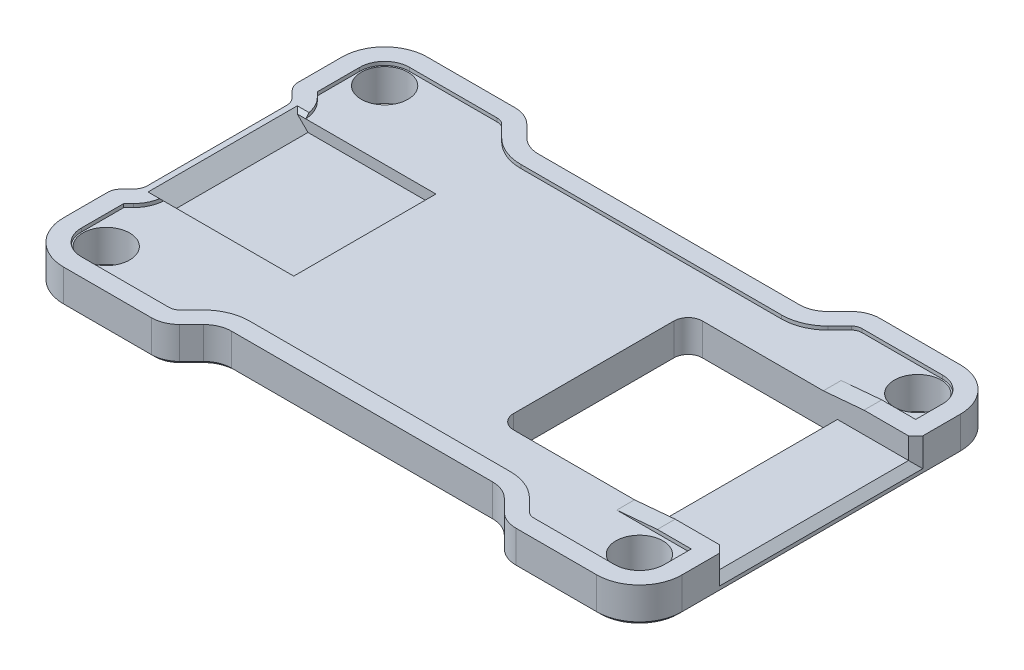
SolidWorks part; units mm, degrees
ref_plane "Front Plane" through (0, 0, 0) normal (0, 0, 1) x (1, 0, 0)
ref_plane "Top Plane" through (0, 0, 0) normal (0, 1, 0) x (1, 0, 0)
ref_plane "Right Plane" through (0, 0, 0) normal (1, 0, 0) x (0, 0, -1)
sketch "Sketch1" plane through (0, 0, 0) normal (0, 1, 0) x (1, 0, 0)
  line L0 (0, -5.29) -> (0, 5.29)
  line L1 (0, 5.29) -> (-1, 6.29)
  line L2 (-1, 6.29) -> (-1, 12.79)
  line L3 (-1, 12.79) -> (9, 12.79)
  line L4 (9, 12.79) -> (11, 10.79)
  line L5 (11, 10.79) -> (31, 10.79)
  line L6 (31, 10.79) -> (33, 12.79)
  line L7 (33, 12.79) -> (42.5, 12.79)
  line L8 (42.5, 12.79) -> (42.5, 6.64)
  line L9 (42.5, 6.64) -> (26.5, 6.64)
  line L10 (26.5, 6.64) -> (26.5, -6.64)
  line L11 (0, 0) -> (36.6809, 0) construction
  line L12 (42.5, -6.64) -> (26.5, -6.64)
  line L13 (42.5, -12.79) -> (42.5, -6.64)
  line L14 (33, -12.79) -> (42.5, -12.79)
  line L15 (31, -10.79) -> (33, -12.79)
  line L16 (11, -10.79) -> (31, -10.79)
  line L17 (9, -12.79) -> (11, -10.79)
  line L18 (-1, -12.79) -> (9, -12.79)
  line L19 (-1, -6.29) -> (-1, -12.79)
  line L20 (0, -5.29) -> (-1, -6.29)
  point P15 (26.5, 0)
  dimension "D1" = 5.29
  dimension "D2" = 1
  dimension "D3" = 1
  dimension "D4" = 6.5
  dimension "D5" = 10
  dimension "D6" = 2
  dimension "D7" = 20
  dimension "D8" = 2
  dimension "D9" = 2
  dimension "D10" = 9.5
  dimension "D11" = 6.15
  dimension "D12" = 16
extrude "Boss-Extrude1" add sketch "Sketch1" along normal blind 2.5
fillet "Fillet1" radius 3 4 edges at (-1, 1.25, -12.79) (42.5, 1.25, -12.79) (42.5, 1.25, 12.79) (-1, 1.25, 12.79)
fillet "Fillet2" radius 1 6 edges at (26.5, 1.25, 6.64) (26.5, 1.25, -6.64) (-1, 1.25, 6.29) (0, 1.25, 5.29) (0, 1.25, -5.29) (-1, 1.25, -6.29)
fillet "Fillet3" radius 2 8 edges at (33, 1.25, 12.79) (31, 1.25, 10.79) (9, 1.25, 12.79) (11, 1.25, 10.79) (33, 1.25, -12.79) (31, 1.25, -10.79) (11, 1.25, -10.79) (9, 1.25, -12.79)
sketch "Sketch3" plane through (0, 0, 0) normal (0, -1, 0) x (1, 0, 0)
  line L0 (42.5, 9.79) -> (42.5, 6.64) construction
  line L1 (42.5, 7.9165) -> (25.7261, 7.9165)
  line L2 (42.5, 7.9165) -> (42.5, -7.5646)
  line L3 (42.5, -7.5646) -> (25.7261, -7.5646)
  line L4 (25.7261, 7.9165) -> (25.7261, -7.5646)
extrude "Boss-Extrude2" add sketch "Sketch3" against normal offset from surface (1 mm away) 1.5 up to face at (18.1733, 2.5, 0)
chamfer "Chamfer1" distance 0.5 angle 45 3 edges at (42.5, 1.75, 6.64) (42.5, 1.75, -6.64) (42.5, 1, 0)
sketch "Sketch5" plane through (0, 2.5, 0) normal (0, 1, 0) x (1, 0, 0)
  line L0 (8.1716, 12.79) -> (2, 12.79) construction
  line L1 (-1, 9.79) -> (-1, 6.7042) construction
  line L2 (2, -12.79) -> (8.1716, -12.79) construction
  line L3 (-1, -6.7042) -> (-1, -9.79) construction
  line L4 (42.5, 7.14) -> (42.5, 9.79) construction
  line L5 (39.5, 12.79) -> (33.8284, 12.79) construction
  line L6 (42.5, -9.79) -> (42.5, -7.14) construction
  line L7 (33.8284, -12.79) -> (39.5, -12.79) construction
  circle A0 centre (2, 9.79) radius 1.65
  circle A1 centre (2, -9.79) radius 1.65
  circle A2 centre (39.5, 9.79) radius 1.65
  circle A3 centre (39.5, -9.79) radius 1.65
  dimension "D1" = 3.3
  dimension "D2" = 3
  dimension "D3" = 3
  dimension "D4" = 3
  dimension "D5" = 3
  dimension "D6" = 3.3
  dimension "D7" = 3
  dimension "D8" = 3
  dimension "D9" = 3.3
  dimension "D10" = 3
  dimension "D11" = 3
  dimension "D12" = 3.3
extrude "Cut-Extrude3" cut sketch "Sketch5" against normal through all
sketch "Sketch6" plane through (0, 2.5, 0) normal (0, 1, 0) x (1, 0, 0)
  line L0 (0, 4.8758) -> (0, -4.8758) construction
  line L1 (0.4, -5) -> (10.4, -5)
  line L2 (0.4, -5) -> (0.4, 5)
  line L3 (0.4, 5) -> (10.4, 5)
  line L4 (10.4, -5) -> (10.4, 5)
  line L5 (0.4, -5) -> (10.4, 5) construction
  line L6 (0.4, 5) -> (10.4, -5) construction
  point P0 (5.4, 0)
  dimension "D1" = 10
  dimension "D2" = 0.4
  dimension "D3" = 10
extrude "Cut-Extrude4" cut sketch "Sketch6" against normal blind 1
chamfer "Chamfer2" distance 0.25 angle 45 3 edges at (5.4, 2.5, 5) (10.4, 2.5, 0) (5.4, 2.5, -5)
chamfer "Chamfer3" distance 0.25 angle 45 32 edges at (41.6213, 0, -11.9113) (36.6642, 0, -12.79) (33.0631, 0, -12.6378) (32, 0, -11.79) (30.9369, 0, -10.9422) (21, 0, -10.79) (11.0631, 0, -10.9422) (10, 0, -11.79) (8.9369, 0, -12.6378) (5.0858, 0, -12.79) (-0.1213, 0, -11.9113) (-1, 0, -8.2471) (-0.9239, 0, -6.3215) (-0.5, 0, -5.79) (-0.0761, 0, -5.2585) (0, 0, 0) (-0.0761, 0, 5.2585) (-0.5, 0, 5.79) (-0.9239, 0, 6.3215) (-1, 0, 8.2471) (42.5, 0, 0) (-0.1213, 0, 11.9113) (41.6213, 0, 11.9113) (5.0858, 0, 12.79) (36.6642, 0, 12.79) (8.9369, 0, 12.6378) (33.0631, 0, 12.6378) (10, 0, 11.79) (32, 0, 11.79) (11.0631, 0, 10.9422) (30.9369, 0, 10.9422) (21, 0, 10.79)
sketch "Sketch7" plane through (0, 1, 0) normal (0, 1, 0) x (1, 0, 0)
  line L0 (27.5, 6.64) -> (42, 6.64) construction
  line L1 (37, 6.64) -> (33, 6.64)
  line L2 (37, 6.64) -> (37, -6.64)
  line L3 (37, -6.64) -> (33, -6.64)
  line L4 (33, 6.64) -> (33, -6.64)
  line L5 (27.5, -6.64) -> (42, -6.64) construction
  line L6 (42.5, 7.14) -> (42.5, -7.14) construction
  dimension "D1" = 5.5
  dimension "D2" = 9.5
extrude "Cut-Extrude5" cut sketch "Sketch7" against normal through all
chamfer "Chamfer4" distance 1 angle 45 1 edges at (0.4, 1.5, 0)
sketch "Sketch8" plane through (0, 2.5, 0) normal (0, 1, 0) x (1, 0, 0)
  line L44 (41.25, -9.79) -> (41.25, -7.89)
  line L45 (41.25, -7.89) -> (27.5, -7.89)
  line L46 (25.25, -5.64) -> (25.25, 5.64)
  line L47 (27.5, 7.89) -> (41.25, 7.89)
  line L48 (41.25, 7.89) -> (41.25, 9.79)
  line L49 (39.5, 11.54) -> (33.8284, 11.54)
  line L50 (33.2981, 11.3203) -> (32.4697, 10.4919)
  line L51 (30.1716, 9.54) -> (11.8284, 9.54)
  line L52 (9.5303, 10.4919) -> (8.7019, 11.3203)
  line L53 (8.1716, 11.54) -> (2, 11.54)
  line L54 (0.25, 9.79) -> (0.25, 6.8078)
  line L55 (0.25, 6.8078) -> (0.591, 6.4668)
  line L56 (1.25, 4.8758) -> (1.25, -4.8758)
  line L57 (0.591, -6.4668) -> (0.25, -6.8078)
  line L58 (0.25, -6.8078) -> (0.25, -9.79)
  line L59 (2, -11.54) -> (8.1716, -11.54)
  line L60 (8.7019, -11.3203) -> (9.5303, -10.4919)
  line L61 (11.8284, -9.54) -> (30.1716, -9.54)
  line L62 (32.4697, -10.4919) -> (33.2981, -11.3203)
  line L63 (33.8284, -11.54) -> (39.5, -11.54)
  line L64 (41.25, -9.79) -> (41.25, -7.89)
  line L65 (41.25, -7.89) -> (27.5, -7.89)
  line L66 (25.25, -5.64) -> (25.25, 5.64)
  line L67 (27.5, 7.89) -> (41.25, 7.89)
  line L68 (41.25, 7.89) -> (41.25, 9.79)
  line L69 (39.5, 11.54) -> (33.8284, 11.54)
  line L70 (33.2981, 11.3203) -> (32.4697, 10.4919)
  line L71 (30.1716, 9.54) -> (11.8284, 9.54)
  line L72 (9.5303, 10.4919) -> (8.7019, 11.3203)
  line L73 (8.1716, 11.54) -> (2, 11.54)
  line L74 (0.25, 9.79) -> (0.25, 6.8078)
  line L75 (0.25, 6.8078) -> (0.591, 6.4668)
  line L76 (1.25, 4.8758) -> (1.25, -4.8758)
  line L77 (0.591, -6.4668) -> (0.25, -6.8078)
  line L78 (0.25, -6.8078) -> (0.25, -9.79)
  line L79 (2, -11.54) -> (8.1716, -11.54)
  line L80 (8.7019, -11.3203) -> (9.5303, -10.4919)
  line L81 (11.8284, -9.54) -> (30.1716, -9.54)
  line L82 (32.4697, -10.4919) -> (33.2981, -11.3203)
  line L83 (33.8284, -11.54) -> (39.5, -11.54)
  arc A36 (25.25, -5.64) -> (27.5, -7.89) centre (27.5, -5.64) ccw
  arc A37 (27.5, 7.89) -> (25.25, 5.64) centre (27.5, 5.64) ccw
  arc A38 (41.25, 9.79) -> (39.5, 11.54) centre (39.5, 9.79) ccw
  arc A39 (33.8284, 11.54) -> (33.2981, 11.3203) centre (33.8284, 10.79) ccw
  arc A40 (30.1716, 9.54) -> (32.4697, 10.4919) centre (30.1716, 12.79) ccw
  arc A41 (9.5303, 10.4919) -> (11.8284, 9.54) centre (11.8284, 12.79) ccw
  arc A42 (8.7019, 11.3203) -> (8.1716, 11.54) centre (8.1716, 10.79) ccw
  arc A43 (2, 11.54) -> (0.25, 9.79) centre (2, 9.79) ccw
  arc A44 (1.25, 4.8758) -> (0.591, 6.4668) centre (-1, 4.8758) ccw
  arc A45 (0.591, -6.4668) -> (1.25, -4.8758) centre (-1, -4.8758) ccw
  arc A46 (0.25, -9.79) -> (2, -11.54) centre (2, -9.79) ccw
  arc A47 (8.1716, -11.54) -> (8.7019, -11.3203) centre (8.1716, -10.79) ccw
  arc A48 (11.8284, -9.54) -> (9.5303, -10.4919) centre (11.8284, -12.79) ccw
  arc A49 (32.4697, -10.4919) -> (30.1716, -9.54) centre (30.1716, -12.79) ccw
  arc A50 (33.2981, -11.3203) -> (33.8284, -11.54) centre (33.8284, -10.79) ccw
  arc A51 (39.5, -11.54) -> (41.25, -9.79) centre (39.5, -9.79) ccw
  arc A52 (25.25, -5.64) -> (27.5, -7.89) centre (27.5, -5.64) ccw
  arc A53 (27.5, 7.89) -> (25.25, 5.64) centre (27.5, 5.64) ccw
  arc A54 (41.25, 9.79) -> (39.5, 11.54) centre (39.5, 9.79) ccw
  arc A55 (33.8284, 11.54) -> (33.2981, 11.3203) centre (33.8284, 10.79) ccw
  arc A56 (30.1716, 9.54) -> (32.4697, 10.4919) centre (30.1716, 12.79) ccw
  arc A57 (9.5303, 10.4919) -> (11.8284, 9.54) centre (11.8284, 12.79) ccw
  arc A58 (8.7019, 11.3203) -> (8.1716, 11.54) centre (8.1716, 10.79) ccw
  arc A59 (2, 11.54) -> (0.25, 9.79) centre (2, 9.79) ccw
  arc A60 (1.25, 4.8758) -> (0.591, 6.4668) centre (-1, 4.8758) ccw
  arc A61 (0.591, -6.4668) -> (1.25, -4.8758) centre (-1, -4.8758) ccw
  arc A62 (0.25, -9.79) -> (2, -11.54) centre (2, -9.79) ccw
  arc A63 (8.1716, -11.54) -> (8.7019, -11.3203) centre (8.1716, -10.79) ccw
  arc A64 (11.8284, -9.54) -> (9.5303, -10.4919) centre (11.8284, -12.79) ccw
  arc A65 (32.4697, -10.4919) -> (30.1716, -9.54) centre (30.1716, -12.79) ccw
  arc A66 (33.2981, -11.3203) -> (33.8284, -11.54) centre (33.8284, -10.79) ccw
  arc A67 (39.5, -11.54) -> (41.25, -9.79) centre (39.5, -9.79) ccw
  dimension "D1" = 1.25
extrude "Cut-Extrude6" cut sketch "Sketch8" against normal blind 0.25
sketch "Sketch10" plane through (0, 1, 0) normal (0, 1, 0) x (1, 0, 0)
  line L8 (27.5, -6.64) -> (33, -6.64)
  line L9 (33, -6.64) -> (33, 6.64)
  line L10 (33, 6.64) -> (27.5, 6.64)
  line L11 (26.5, 5.64) -> (26.5, -5.64)
  line L12 (27.5, -6.64) -> (33, -6.64)
  line L13 (33, -6.64) -> (33, 6.64)
  line L14 (33, 6.64) -> (27.5, 6.64)
  line L15 (26.5, 5.64) -> (26.5, -5.64)
  arc A4 (27.5, 6.64) -> (26.5, 5.64) centre (27.5, 5.64) ccw
  arc A5 (26.5, -5.64) -> (27.5, -6.64) centre (27.5, -5.64) ccw
  arc A6 (27.5, 6.64) -> (26.5, 5.64) centre (27.5, 5.64) ccw
  arc A7 (26.5, -5.64) -> (27.5, -6.64) centre (27.5, -5.64) ccw
  dimension "D1" = 0
extrude "Cut-Extrude8" cut sketch "Sketch10" against normal blind 10
sketch "Sketch11" plane through (0, 2.5, 0) normal (0, 1, 0) x (1, 0, 0)
  line L1 (16.1939, -8.335) -> (35.8659, -8.335)
  line L2 (16.1939, -8.335) -> (16.1939, 8.335)
  line L3 (16.1939, 8.335) -> (35.8659, 8.335)
  line L4 (35.8659, -8.335) -> (35.8659, 8.335)
  line L5 (16.1939, -8.335) -> (35.8659, 8.335) construction
  line L6 (16.1939, 8.335) -> (35.8659, -8.335) construction
  point P0 (26.0299, 0)
extrude "Cut-Extrude9" cut sketch "Sketch11" against normal up to surface (0.25 mm away) up to face at (18.7977, 2.25, 0)
chamfer "Chamfer5" distance 3 angle 5 2 edges at (35.8659, 2.5, 7.265) (35.8659, 2.5, -7.265) first distance on face at (18.9199, 2.5, 0)
